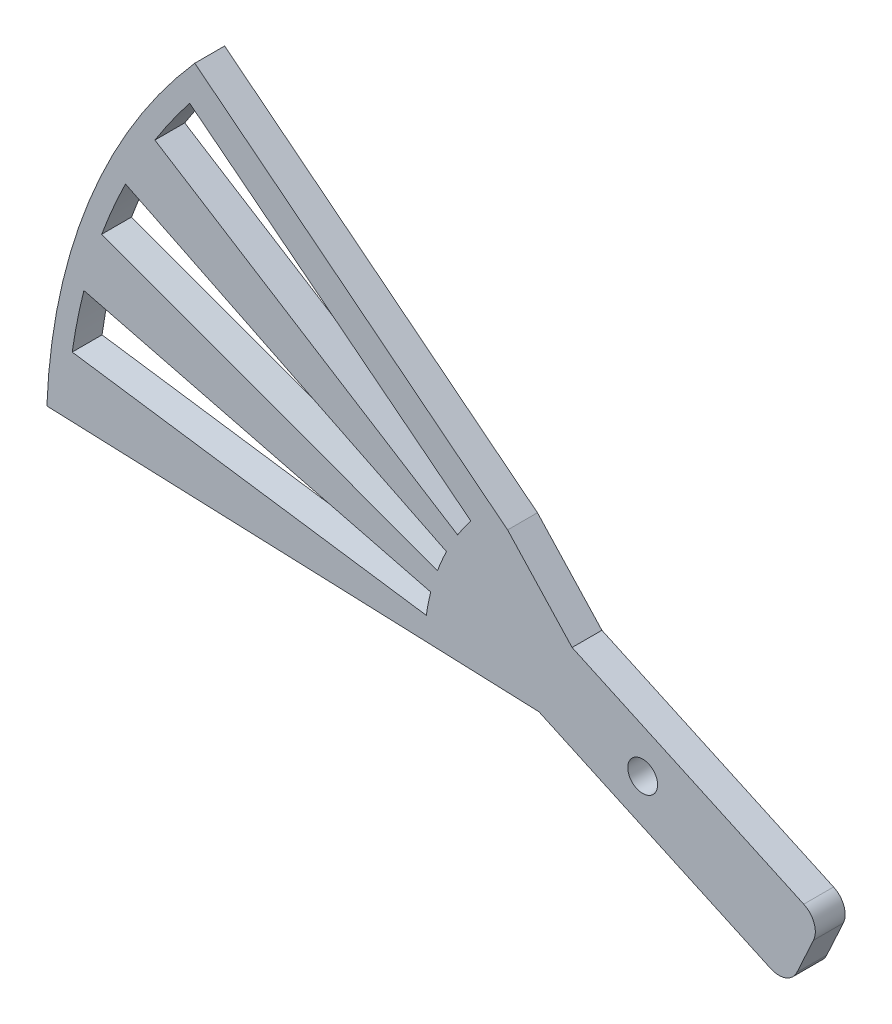
SolidWorks part; units mm, degrees
ref_plane "Front Plane" through (0, 0, 0) normal (0, 0, 1) x (1, 0, 0)
ref_plane "Top Plane" through (0, 0, 0) normal (0, 1, 0) x (1, 0, 0)
ref_plane "Right Plane" through (0, 0, 0) normal (1, 0, 0) x (0, 0, -1)
sketch "Sketch1" plane through (0, 0, 0) normal (0, 0, 1) x (1, 0, 0)
  line L0 (-19.9854, 0.7628) -> (-59.9563, 2.2884)
  line L1 (-16.3569, 14.7123) -> (-16.1915, 14.8941)
  line L2 (0, 0) -> (-50.7795, 31.96) construction
  line L3 (0, 0) -> (-57.3211, 17.7283) construction
  line L4 (-21.8167, 2.8342) -> (-57.8471, 4.2094)
  line L5 (-13.5925, 14.6712) -> (-45.0737, 39.6026)
  line L6 (-21.2283, 5.7759) -> (-57.2696, 9.1759)
  line L7 (-57.0177, 18.6812) -> (-57.0256, 18.6836)
  line L8 (-20.7005, 7.449) -> (-55.1067, 18.0901)
  line L9 (-19.4947, 10.196) -> (-53.3439, 22.7691)
  line L10 (-18.0672, 12.5529) -> (-48.5469, 31.7364)
  line L11 (-50.2398, 32.8019) -> (-50.2468, 32.8063)
  line L12 (0.5327, 0.8463) -> (-50.2468, 32.8063) construction
  line L13 (-16.1915, 14.8941) -> (-45.6332, 35.7997)
  line L15 (-16.3569, 14.7123) -> (-40.8618, 41.162) construction
  line L16 (-13.5925, 14.6712) -> (-40.7774, 44.0137) construction
  line L18 (-54.5167, 25.0585) -> (22.4523, -10.3202) construction
  line L19 (14.6844, -11.152) -> (18.0256, -3.8831)
  line L20 (-7.1038, 7.6676) -> (-13.5925, 14.6712)
  line L21 (-18.9747, 13.124) -> (-16.1345, 11.8185)
  line L22 (-7.1038, 7.6676) -> (18.0256, -3.8831)
  line L23 (-10.4449, 0.3987) -> (-19.9854, 0.7628)
  line L24 (-10.4449, 0.3987) -> (14.6844, -11.152)
  line L25 (-22.3798, 5.8845) -> (-19.4756, 4.5496)
  arc A0 (-45.0737, 39.6026) -> (-59.9563, 2.2884) centre (0, 0) ccw
  arc A1 (-13.5925, 14.6712) -> (-19.9854, 0.7628) centre (0, 0) ccw
  arc A2 (-45.6332, 35.7997) -> (-48.5469, 31.7364) centre (0, 0) ccw
  arc A3 (-16.3569, 14.7123) -> (-18.0672, 12.5529) centre (0, 0) ccw
  arc A4 (-53.3439, 22.7691) -> (-55.1067, 18.0901) centre (0, 0) ccw
  arc A5 (-40.8618, 41.162) -> (-57.8471, 4.2094) centre (0, 0) ccw construction
  arc A6 (-19.4947, 10.196) -> (-20.7005, 7.449) centre (0, 0) ccw
  arc A7 (-21.2283, 5.7759) -> (-21.8167, 2.8342) centre (0, 0) ccw
  arc A8 (-16.3569, 14.7123) -> (-21.8167, 2.8342) centre (0, 0) ccw construction
  arc A9 (-57.2696, 9.1759) -> (-57.8471, 4.2094) centre (0, 0) ccw
  circle A10 centre (0, 0) radius 1.5
  arc A11 (-40.7774, 44.0137) -> (-59.9563, 2.2884) centre (0, 0) ccw construction
  point P16 (0.2955, 0.9554)
  point P33 (-56.1873, 21.4241)
  point P34 (20.7818, -13.9546)
  point P35 (-52.8461, 28.693)
  point P36 (24.1229, -6.6857)
  dimension "D1" = 120
  dimension "D2" = 40
  dimension "D16" = 3
  dimension "D3" = 0.2459
  dimension "D4" = 15
  dimension "D5" = 2
  dimension "15" = 15
  dimension "D6" = 3
  dimension "D7" = 5
  dimension "D8" = 3
  dimension "D9" = 5
  dimension "D11" = 3
  dimension "D12" = 5
  dimension "D13" = 3
  dimension "D15" = 18
  dimension "D10" = 1
extrude "Boss-Extrude2" add sketch "Sketch1" along normal blind 3 contours L0 A0 L5 A1
extrude "Boss-Extrude5" add sketch "Sketch1<8>" along normal blind 3 contours L20 A1 L23 L24 L19 L22 A10 region at (-2.3746, 1.0915, 0)
sketch "Sketch1<8>" plane through (0, 0, 0) normal (0, 0, 1) x (1, 0, 0) same geometry as "Sketch1"
fillet "Fillet1" radius 2 2 edges at (18.0256, -3.8831, 1.5) (14.6844, -11.152, 1.5)
sketch "Sketch2" plane through (0, 0, 3) normal (0, 0, 1) x (1, 0, 0)
  line L0 (-52.0473, 25.5944) -> (-19.7421, 9.7082)
  line L1 (-54.4376, 20.0138) -> (-20.6487, 7.5914)
  line L2 (-56.2314, 14.2139) -> (-21.3291, 5.3915)
  line L3 (-57.4091, 8.2583) -> (-21.7759, 3.1324)
  line L4 (-49.0869, 30.8947) -> (-18.6192, 11.7187)
  line L5 (-45.5886, 35.8564) -> (-17.2922, 13.6007)
  arc A0 (-21.3291, 5.3915) -> (-21.7759, 3.1324) centre (0, 0) ccw
  arc A1 (-21.3291, 5.3915) -> (-21.7759, 3.1324) centre (0, 0) ccw construction
  arc A2 (-19.7421, 9.7082) -> (-20.6487, 7.5914) centre (0, 0) ccw
  arc A3 (-19.7421, 9.7082) -> (-20.6487, 7.5914) centre (0, 0) ccw construction
  arc A4 (-17.2922, 13.6007) -> (-18.6192, 11.7187) centre (0, 0) ccw
  arc A5 (-17.2922, 13.6007) -> (-18.6192, 11.7187) centre (0, 0) ccw construction
  arc A6 (-56.2314, 14.2139) -> (-57.4091, 8.2583) centre (0, 0) ccw
  arc A7 (-56.2314, 14.2139) -> (-57.4091, 8.2583) centre (0, 0) ccw construction
  arc A8 (-52.0473, 25.5944) -> (-54.4376, 20.0138) centre (0, 0) ccw
  arc A9 (-52.0473, 25.5944) -> (-54.4376, 20.0138) centre (0, 0) ccw construction
  arc A10 (-45.5886, 35.8564) -> (-49.0869, 30.8947) centre (0, 0) ccw
  arc A11 (-45.5886, 35.8564) -> (-49.0869, 30.8947) centre (0, 0) ccw construction
extrude "Cut-Extrude1" cut sketch "Sketch2" against normal up to next
